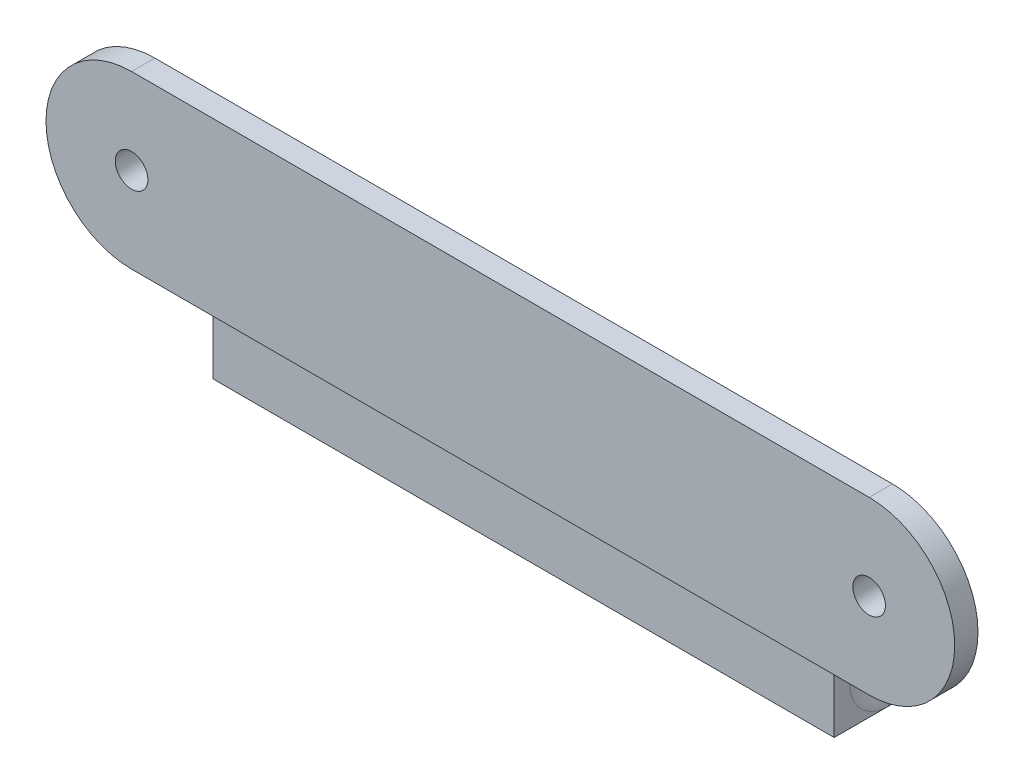
SolidWorks part; units mm, degrees
ref_plane "Front Plane" through (0, 0, 0) normal (0, 0, 1) x (1, 0, 0)
ref_plane "Top Plane" through (0, 0, 0) normal (0, 1, 0) x (1, 0, 0)
ref_plane "Right Plane" through (0, 0, 0) normal (1, 0, 0) x (0, 0, -1)
sketch "Sketch1" plane through (0, 0, 0) normal (0, 0, 1) x (1, 0, 0)
  line L0 (0, 0) -> (95, 0) construction
  line L1 (0, 11.0235) -> (95, 11.0235)
  line L2 (0, -11.0235) -> (95, -11.0235)
  arc A0 (0, 11.0235) -> (0, -11.0235) centre (0, 0) ccw
  arc A1 (95, -11.0235) -> (95, 11.0235) centre (95, 0) ccw
  circle A2 centre (0, 0) radius 2.1
  circle A3 centre (95, 0) radius 2.1
  point P3 (47.5, 0)
  dimension "D2" = 4.2
  dimension "D1" = 95
extrude "Boss-Extrude1" add sketch "Sketch1" along normal blind 3
sketch3d "3DSketch1"
  line L1 (47.5, 3.9765, 0) -> (47.5, 3.9765, -5)
  line L2 (47.5, 3.9765, 0) -> (47.5, -21.0235, 0)
  line L3 (47.5, -21.0235, 0) -> (47.5, -21.0235, -5)
  line L4 (47.5, 3.9765, -5) -> (47.5, -21.0235, -5)
  dimension "D1" = 47.5
  dimension "D2" = 5
  dimension "D3" = 25
extrude "Boss-Extrude2" add sketch "3DSketch1" along direction (1, 0, 0) on the side of the normal mid plane 80 contours L2 L1 L4 L3
fillet "Fillet1" radius 18 1 edges
sketch "Sketch2" plane through (0, 0, -5) normal (0, 0, -1) x (-1, 0, 0)
  line L0 (-7.5, -8.4734) -> (-7.5, -21.0235) construction
  line L1 (-87.5, -21.0235) -> (-7.5, -21.0235)
  line L2 (-87.5, -21.0235) -> (-87.5, -18.0235)
  line L3 (-87.5, -18.0235) -> (-7.5, -18.0235)
  line L4 (-7.5, -21.0235) -> (-7.5, -18.0235)
  dimension "D1" = 3
extrude "Boss-Extrude3" add sketch "Sketch2" along normal blind 8
fillet "Fillet2" radius 2 1 edges at (47.5, -18.0235, -5)
sketch "Sketch3" plane through (0, -18.0235, 0) normal (0, 1, 0) x (1, 0, 0)
  line L0 (47.5, 13) -> (47.5, 7) construction
  line L1 (7.5, 13) -> (87.5, 13) construction
  line L2 (7.5, 7) -> (87.5, 7) construction
  circle A0 centre (17.5, 10.1253) radius 1.6
  circle A1 centre (77.5, 10.1253) radius 1.6
  point P10 (0, 0)
  point P11 (12.7573, 9.5072)
  point P12 (0, 0)
  point P13 (11.3289, 9.5072)
  point P14 (12.5, 9.6753)
  point P15 (12.5, 10.1253)
  dimension "D1" = 3.2
  dimension "D2" = 60
extrude "Cut-Extrude1" cut sketch "Sketch3" against normal through all both and the other way through all
fillet "Fillet3" radius 3 8 edges at (7.5, -18.0235, -10) (7.5, -17.4377, -5.5858) (87.5, -18.0235, -10) (87.5, -17.4377, -5.5858)
